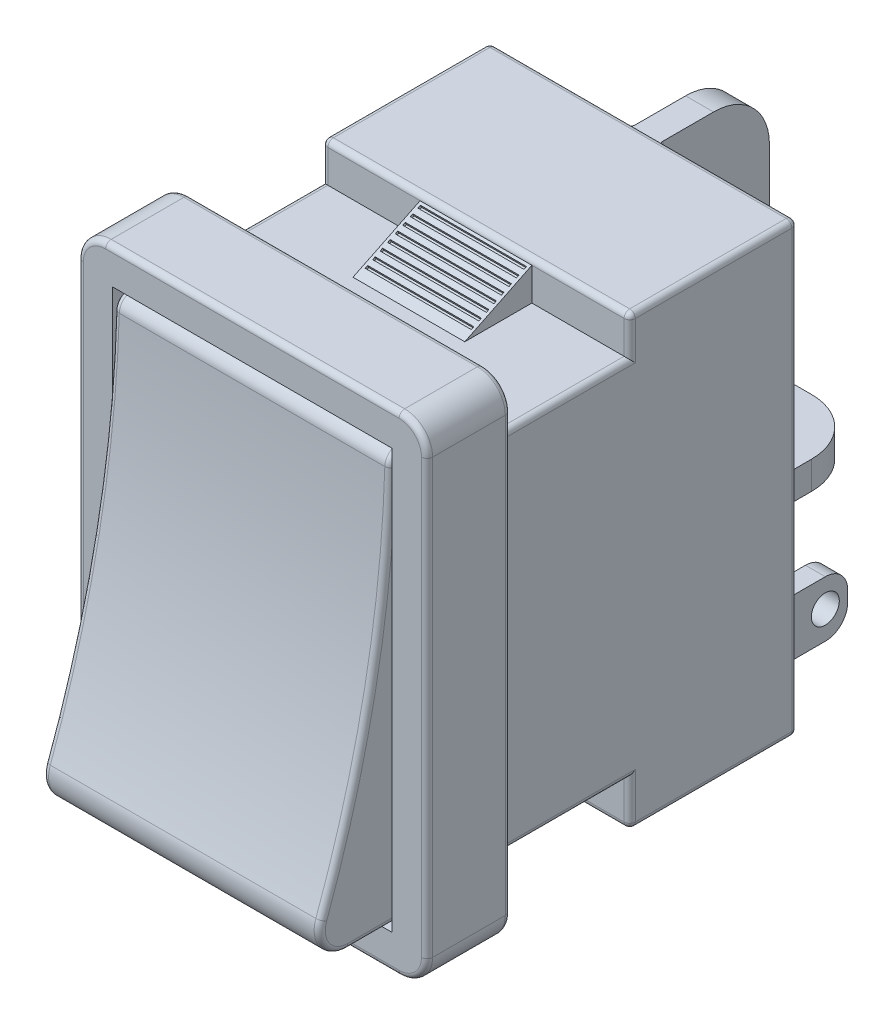
SolidWorks part; units mm, degrees
ref_plane "Front Plane" through (0, 0, 0) normal (0, 0, 1) x (1, 0, 0)
ref_plane "Top Plane" through (0, 0, 0) normal (0, 1, 0) x (1, 0, 0)
ref_plane "Right Plane" through (0, 0, 0) normal (1, 0, 0) x (0, 0, -1)
sketch "Sketch1" plane through (0, 0, 0) normal (0, 0, 1) x (1, 0, 0)
  line L1 (-62.5, -87.5) -> (62.5, -87.5)
  line L2 (-62.5, -87.5) -> (-62.5, 87.5)
  line L3 (-62.5, 87.5) -> (62.5, 87.5)
  line L4 (62.5, -87.5) -> (62.5, 87.5)
  line L5 (-62.5, -87.5) -> (62.5, 87.5) construction
  line L6 (-62.5, 87.5) -> (62.5, -87.5) construction
  point P0 (0, 0)
  dimension "D1" = 125
  dimension "D2" = 175
extrude "Boss-Extrude1" add sketch "Sketch1" along normal blind 30
fillet "Fillet1" radius 10 4 edges at (-62.5, 87.5, 15) (-62.5, -87.5, 15) (62.5, -87.5, 15) (62.5, 87.5, 15)
fillet "Fillet2" radius 2 16 edges at (-59.5711, -84.5711, 0) (0, -87.5, 0) (59.5711, -84.5711, 0) (62.5, 0, 0) (59.5711, 84.5711, 0) (0, 87.5, 0) (-59.5711, 84.5711, 0) (-62.5, 0, 0) (59.5711, 84.5711, 30) (62.5, 0, 30) (59.5711, -84.5711, 30) (0, -87.5, 30) (-59.5711, -84.5711, 30) (-62.5, 0, 30) (-59.5711, 84.5711, 30) (0, 87.5, 30)
sketch "Sketch2" plane through (0, 0, 0) normal (1, 0, 0) x (0, 0, -1)
  line L0 (0, 0) -> (137.8465, 0) construction
  line L2 (0, 65) -> (50, 65)
  line L3 (0, 77.5) -> (0, -77.5) construction
  line L4 (50, 65) -> (50, 78.7053)
  line L5 (50, 78.7053) -> (110, 78.7053)
  line L6 (110, 78.7053) -> (110, -81.2947)
  line L7 (110, -81.2947) -> (50, -81.2947)
  line L8 (50, -81.2947) -> (50, -65)
  line L9 (50, -65) -> (0, -65)
  line L10 (0, -65) -> (0, 65)
  point P12 (25, -65)
  dimension "D1" = 160
  dimension "D2" = 60
  dimension "D3" = 50
  dimension "D4" = 50
  dimension "D5" = 130
extrude "Boss-Extrude2" add sketch "Sketch2" along normal mid plane 110
fillet "Fillet3" radius 2 22 edges at (55, 0, 0) (0, -65, 0) (0, 65, 0) (-55, -65, -25) (-55, -73.1474, -50) (-55, -81.2947, -80) (-55, -1.2947, -110) (-55, 78.7053, -80) (-55, 71.8526, -50) (-55, 65, -25) (-55, 0, 0) (55, 71.8526, -50) (55, 65, -25) (55, -65, -25) (55, -73.1474, -50) (55, -81.2947, -80) (55, -1.2947, -110) (55, 78.7053, -80) (0, -81.2947, -110) (0, 78.7053, -110) (0, -81.2947, -50) (0, 78.7053, -50)
sketch "Sketch3" plane through (0, 0, -110) normal (0, 0, -1) x (-1, 0, 0)
  line L0 (53, 76.7053) -> (-53, 76.7053) construction
  line L1 (-5, 76.7053) -> (5, 76.7053)
  line L2 (-5, 76.7053) -> (-5, -13.2947)
  line L3 (5, -13.2947) -> (40.1095, -13.2947)
  line L4 (5, 76.7053) -> (5, -13.2947)
  line L5 (0, 0) -> (0, 89.7403) construction
  line L7 (-40.1095, -13.2947) -> (-5, -13.2947)
  line L8 (-40.1095, -13.2947) -> (-40.1095, -23.2947)
  line L9 (-40.1095, -23.2947) -> (40.1095, -23.2947)
  line L10 (40.1095, -13.2947) -> (40.1095, -23.2947)
  dimension "D2" = 10
  dimension "D3" = 100
extrude "Boss-Extrude3" add sketch "Sketch3" along normal blind 40
fillet "Fillet4" radius 20 3 edges at (-40.1095, -18.2947, -150) (40.1095, -18.2947, -150) (0, 76.7053, -150)
fillet "Fillet5" radius 2 7 edges at (22.5548, -13.2947, -110) (40.1095, -18.2947, -110) (0, -23.2947, -110) (-40.1095, -18.2947, -110) (-22.5548, -13.2947, -110) (-5, 31.7053, -110) (5, 31.7053, -110)
sketch "Sketch4" plane through (0, 0, 0) normal (1, 0, 0) x (0, 0, -1)
  line L0 (50, 76.7053) -> (26, 65)
  line L1 (2, 65) -> (50, 65) construction
  line L2 (26, 65) -> (50, 65)
  line L3 (50, 65) -> (50, 76.7053)
extrude "Boss-Extrude4" add sketch "Sketch4" along normal mid plane 40
sketch "Sketch5" plane through (0, 42.2655, 20.6138) normal (0, 0.8988, 0.4384) x (1, 0, 0)
  line L0 (20, 78.5646) -> (20, 51.8623) construction
  line L1 (-19, 77.5646) -> (19, 77.5646)
  line L2 (-19, 77.5646) -> (-19, 76.5646)
  line L3 (-19, 76.5646) -> (19, 76.5646)
  line L4 (19, 77.5646) -> (19, 76.5646)
  line L5 (20, 78.5646) -> (-20, 78.5646) construction
  line L6 (-20, 73.4335) -> (-20, 78.5646) construction
  point P4 (18.259, 74.2609)
  dimension "D1" = 1
  dimension "D2" = 1
  dimension "D3" = 1
  dimension "D4" = 1
extrude "Cut-Extrude1" cut sketch "Sketch5" against normal blind 1
pattern_linear "LPattern1" count 8 spacing 3 along (0, -0.4384, 0.8988) of "Cut-Extrude1"
sketch "Sketch6" plane through (0, 0, -110) normal (0, 0, -1) x (-1, 0, 0)
  line L0 (-53, 76.7053) -> (-53, -79.2947) construction
  line L1 (-43, -49.2947) -> (-35.8919, -49.2947)
  line L2 (-43, -49.2947) -> (-43, -69.2947)
  line L3 (-43, -69.2947) -> (-35.8919, -69.2947)
  line L4 (-35.8919, -49.2947) -> (-35.8919, -69.2947)
  line L5 (-53, -79.2947) -> (53, -79.2947) construction
  dimension "D1" = 10
  dimension "D2" = 10
  dimension "D3" = 20
extrude "Boss-Extrude5" add sketch "Sketch6" along normal blind 30 separate body
fillet "Fillet6" radius 8 2 edges at (39.4459, -69.2947, -140) (39.4459, -49.2947, -140)
sketch "Sketch7" plane through (43, 0, 0) normal (1, 0, 0) x (0, 0, -1)
  circle A0 centre (132, -59.2947) radius 5
  dimension "D1" = 10
extrude "Cut-Extrude2" cut sketch "Sketch7" against normal blind 30
sketch "Sketch8" plane through (0, 0, -110) normal (0, 0, -1) x (-1, 0, 0)
  line L0 (-35.8919, -69.2947) -> (-35.8919, -61.2947) construction
  line L1 (-35.8919, -69.2947) -> (-43, -69.2947)
  line L2 (-35.8919, -69.2947) -> (-35.8919, -49.2947)
  line L3 (-35.8919, -49.2947) -> (-43, -49.2947)
  line L4 (-43, -69.2947) -> (-43, -49.2947)
  line L5 (-43, -49.2947) -> (-43, -57.2947) construction
  line L6 (-43, -49.2947) -> (-35.8919, -49.2947) construction
  line L7 (-35.8919, -69.2947) -> (-43, -69.2947) construction
  line L8 (-34.8919, -48.2947) -> (-44, -48.2947)
  line L9 (-44, -70.2947) -> (-44, -48.2947)
  line L10 (-34.8919, -70.2947) -> (-44, -70.2947)
  line L11 (-34.8919, -70.2947) -> (-34.8919, -48.2947)
  dimension "D1" = 1
extrude "Boss-Extrude6" add sketch "Sketch8" along normal blind 2
mirror "Mirror1" about plane through (0, 0, 0) normal (1, 0, 0) of "Boss-Extrude6"
mirror "Mirror2" about plane through (0, 0, 0) normal (1, 0, 0) of bodies 108
sketch "Sketch9" plane through (0, 0, 30) normal (0, 0, 1) x (1, 0, 0)
  line L1 (-50, -75) -> (50, -75)
  line L2 (-50, -75) -> (-50, 75)
  line L3 (-50, 75) -> (50, 75)
  line L4 (50, -75) -> (50, 75)
  line L5 (-50, -75) -> (50, 75) construction
  line L6 (-50, 75) -> (50, -75) construction
  point P0 (0, 0)
  dimension "D1" = 100
  dimension "D2" = 150
extrude "Cut-Extrude3" cut sketch "Sketch9" against normal blind 20
sketch "Sketch10" plane through (0, 0, 0) normal (1, 0, 0) x (0, 0, -1)
  line L0 (-30, 73) -> (-10, 73)
  line L1 (-30, -77.5) -> (-30, 77.5) construction
  line L2 (-10, -75) -> (-10, 75) construction
  line L3 (-10, 73) -> (-10, -73)
  line L4 (-10, -73) -> (-45.3999, -73)
  line L5 (-10, -75) -> (-30, -75) construction
  line L6 (-10, 75) -> (-30, 75) construction
  arc A0 (-30, 73) -> (-54.7866, -59.5519) centre (-435.1448, 80.1667) cw
  arc A1 (-45.3999, -73) -> (-54.7866, -59.5519) centre (-45.3999, -63) cw
  point P15 (-60, -73)
  dimension "D4" = 10
  dimension "D1" = 2
  dimension "D2" = 2
  dimension "D3" = 50
extrude "Boss-Extrude7" add sketch "Sketch10" along normal mid plane 99 separate body
fillet "Fillet7" radius 5 1 edges at (0, 73, 30)
fillet "Fillet8" radius 2 10 edges at (-49.5, 73, 17.5585) (-49.5, 71.5876, 28.5998) (-49.5, -73, 27.6999) (-49.5, -68.7236, 53.5999) (49.5, 73, 17.5585) (49.5, 71.5876, 28.5998) (49.5, -73, 27.6999) (49.5, -68.7236, 53.5999) (-49.5, 3.3019, 37.2937) (49.5, 3.3019, 37.2937)
